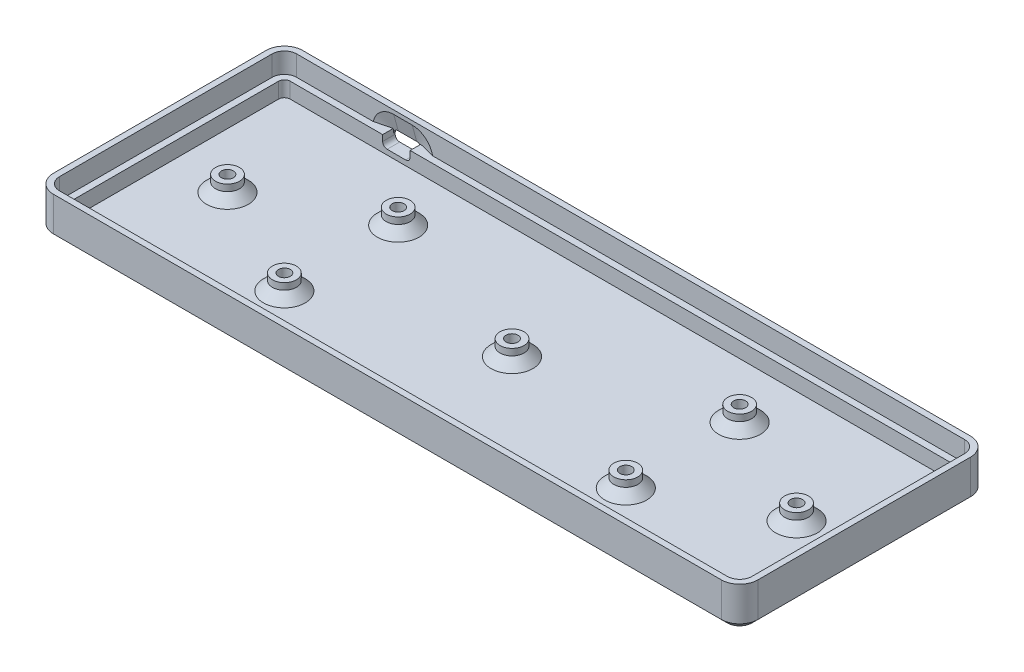
SolidWorks part; units mm, degrees
ref_plane "Alzado" through (0, 0, 0) normal (0, 0, 1) x (1, 0, 0)
ref_plane "Planta" through (0, 0, 0) normal (0, 1, 0) x (1, 0, 0)
ref_plane "Vista lateral" through (0, 0, 0) normal (1, 0, 0) x (0, 0, -1)
sketch "Reference" plane through (0, 0, 0) normal (0, 1, 0) x (1, 0, 0)
  point P0 (0, 0)
  line B0 (-40.625, -35.575) -> (-40.625, -21.575)
  line B1 (-59.675, -35.575) -> (-59.675, -21.575)
  line B2 (-113.775, -35.575) -> (-113.775, 28.575)
  line B3 (-92.725, 16.525) -> (-92.725, 2.525)
  line B4 (-111.775, 37.575) -> (111.775, 37.575)
  circle B5 centre (-104.775, 9.525) radius 2
  line B6 (111.775, -37.575) -> (-111.775, -37.575)
  line B7 (73.675, -21.575) -> (59.675, -21.575)
  circle B8 centre (66.675, -9.525) radius 2
  line B9 (73.675, -2.525) -> (59.675, -2.525)
  line B10 (59.675, 2.525) -> (73.675, 2.525)
  line B11 (73.675, 2.525) -> (73.675, 16.525)
  circle B12 centre (66.675, 9.525) radius 2
  line B13 (73.675, 16.525) -> (59.675, 16.525)
  circle B14 centre (57.15, 19.05) radius 1.35
  line B15 (-40.625, 35.575) -> (-54.625, 35.575)
  line B16 (-97.775, 21.575) -> (-97.775, 35.575)
  circle B17 centre (-104.775, 28.575) radius 2
  line B18 (-111.775, 21.575) -> (-97.775, 21.575)
  line B19 (-97.775, 35.575) -> (-111.775, 35.575)
  line B20 (-111.775, 35.575) -> (-111.775, 21.575)
  line B21 (-113.775, 28.575) -> (-113.775, 35.575)
  arc B22 (-111.775, 37.575) -> (-113.775, 35.575) centre (-111.775, 35.575) ccw
  line B23 (-111.775, 16.525) -> (-111.775, 2.525)
  line B24 (-111.775, 2.525) -> (-97.775, 2.525)
  line B25 (-97.775, -16.525) -> (-97.775, -2.525)
  line B26 (-92.725, -16.525) -> (-78.725, -16.525)
  line B27 (-78.725, -21.575) -> (-92.725, -21.575)
  circle B28 centre (-85.725, -28.575) radius 2
  line B29 (-92.725, -35.575) -> (-78.725, -35.575)
  arc B30 (-113.775, -35.575) -> (-111.775, -37.575) centre (-111.775, -35.575) ccw
  line B31 (-111.775, -35.575) -> (-97.775, -35.575)
  circle B32 centre (-104.775, -28.575) radius 2
  line B33 (-97.775, -21.575) -> (-111.775, -21.575)
  circle B34 centre (-104.775, -9.525) radius 2
  line B35 (-111.775, -16.525) -> (-97.775, -16.525)
  line B36 (-97.775, -35.575) -> (-97.775, -21.575)
  line B37 (-92.725, -21.575) -> (-92.725, -35.575)
  arc B38 (111.775, -37.575) -> (113.775, -35.575) centre (111.775, -35.575) ccw
  line B39 (113.775, 35.575) -> (113.775, -35.575)
  arc B40 (113.775, 35.575) -> (111.775, 37.575) centre (111.775, 35.575) ccw
  line B41 (111.775, 35.575) -> (97.775, 35.575)
  line B42 (97.775, 35.575) -> (97.775, 21.575)
  line B43 (73.675, 21.575) -> (73.675, 35.575)
  circle B44 centre (66.675, 28.575) radius 2
  circle B45 centre (28.575, 28.575) radius 2
  line B46 (-16.525, 35.575) -> (-16.525, 21.575)
  line B47 (-59.675, 35.575) -> (-73.675, 35.575)
  circle B48 centre (-66.675, 28.575) radius 2
  line B49 (-73.675, 35.575) -> (-73.675, 21.575)
  line B50 (-78.725, 2.525) -> (-78.725, 16.525)
  circle B51 centre (-85.725, 9.525) radius 2
  line B52 (-92.725, 2.525) -> (-78.725, 2.525)
  circle B53 centre (-95.25, 0) radius 1.35
  line B54 (-97.775, -2.525) -> (-111.775, -2.525)
  circle B55 centre (-85.725, 28.575) radius 2
  line B56 (-78.725, 21.575) -> (-78.725, 35.575)
  line B57 (-54.625, 35.575) -> (-54.625, 21.575)
  line B58 (-54.625, 21.575) -> (-40.625, 21.575)
  line B59 (-40.625, 16.525) -> (-54.625, 16.525)
  line B60 (-92.725, 35.575) -> (-92.725, 21.575)
  line B61 (-2.525, -16.525) -> (-2.525, -2.525)
  line B62 (16.525, -16.525) -> (16.525, -2.525)
  line B63 (40.625, 2.525) -> (54.625, 2.525)
  line B64 (54.625, 2.525) -> (54.625, 16.525)
  circle B65 centre (47.625, 9.525) radius 2
  line B66 (40.625, 16.525) -> (40.625, 2.525)
  line B67 (35.575, 16.525) -> (21.575, 16.525)
  line B68 (16.525, 16.525) -> (2.525, 16.525)
  line B69 (-16.525, 21.575) -> (-2.525, 21.575)
  circle B70 centre (-28.575, 28.575) radius 2
  line B71 (-21.575, 16.525) -> (-35.575, 16.525)
  circle B72 centre (-57.15, 19.05) radius 1.35
  line B73 (97.775, -35.575) -> (111.775, -35.575)
  line B74 (111.775, -35.575) -> (111.775, -21.575)
  line B75 (111.775, -21.575) -> (97.775, -21.575)
  line B76 (97.775, -2.525) -> (97.775, -16.525)
  line B77 (92.725, 16.525) -> (78.725, 16.525)
  line B78 (78.725, 35.575) -> (78.725, 21.575)
  line B79 (8.438, -18.175) -> (-8.438, -18.175)
  line B80 (7, -21.575) -> (-7, -21.575)
  circle B81 centre (0, -28.575) radius 2
  line B82 (-7, -35.575) -> (7, -35.575)
  line B83 (-111.775, -21.575) -> (-111.775, -35.575)
  line B84 (59.675, 21.575) -> (73.675, 21.575)
  line B85 (59.675, 35.575) -> (59.675, 21.575)
  circle B86 centre (47.625, 28.575) radius 2
  circle B87 centre (-66.675, 9.525) radius 2
  line B88 (-73.675, 16.525) -> (-73.675, 2.525)
  line B89 (-78.725, 16.525) -> (-92.725, 16.525)
  line B90 (-76.2, 39.575) -> (-76.2, 41.575)
  line B91 (-71.2, 39.575) -> (-81.2, 39.575)
  line B92 (-76.2, 37.575) -> (-76.2, 39.575)
  line B93 (-97.775, 2.525) -> (-97.775, 16.525)
  line B94 (-40.625, 21.575) -> (-40.625, 35.575)
  line B95 (-78.725, 35.575) -> (-92.725, 35.575)
  line B96 (-35.575, -35.575) -> (-21.575, -35.575)
  circle B97 centre (-28.575, -28.575) radius 2
  line B98 (-35.575, -21.575) -> (-35.575, -35.575)
  circle B99 centre (-47.625, 28.575) radius 2
  line B100 (-59.675, -21.575) -> (-73.675, -21.575)
  line B101 (-73.675, -16.525) -> (-59.675, -16.525)
  line B102 (-59.675, -2.525) -> (-73.675, -2.525)
  line B103 (-59.675, 2.525) -> (-59.675, 16.525)
  line B104 (-59.675, 21.575) -> (-59.675, 35.575)
  line B105 (-111.775, -2.525) -> (-111.775, -16.525)
  line B106 (-73.675, 21.575) -> (-59.675, 21.575)
  line B107 (-59.675, 16.525) -> (-73.675, 16.525)
  line B108 (-59.675, -16.525) -> (-59.675, -2.525)
  line B109 (-81.2, 39.575) -> (-81.2, 37.575)
  line B110 (-92.725, 21.575) -> (-78.725, 21.575)
  circle B111 centre (-47.625, 9.525) radius 2
  line B112 (-54.625, 16.525) -> (-54.625, 2.525)
  line B113 (-97.775, 16.525) -> (-111.775, 16.525)
  line B114 (-35.575, 16.525) -> (-35.575, 2.525)
  circle B115 centre (-9.525, 9.525) radius 2
  line B116 (2.525, 16.525) -> (2.525, 2.525)
  line B117 (97.775, -21.575) -> (97.775, -35.575)
  circle B118 centre (85.725, -28.575) radius 2
  line B119 (73.675, -35.575) -> (73.675, -21.575)
  line B120 (40.625, -16.525) -> (54.625, -16.525)
  line B121 (21.575, -16.525) -> (35.575, -16.525)
  circle B122 centre (47.625, -9.525) radius 2
  line B123 (54.625, -16.525) -> (54.625, -2.525)
  line B124 (35.575, -16.525) -> (35.575, -2.525)
  line B125 (16.525, -2.525) -> (2.525, -2.525)
  line B126 (-16.525, 2.525) -> (-2.525, 2.525)
  line B127 (-21.575, 2.525) -> (-21.575, 16.525)
  line B128 (-54.625, 2.525) -> (-40.625, 2.525)
  line B129 (-40.625, -2.525) -> (-54.625, -2.525)
  circle B130 centre (-47.625, -9.525) radius 2
  line B131 (-54.625, -16.525) -> (-40.625, -16.525)
  line B132 (-40.625, -21.575) -> (-54.625, -21.575)
  line B133 (-54.625, -21.575) -> (-54.625, -35.575)
  circle B134 centre (-57.15, -19.05) radius 1.35
  circle B135 centre (-85.725, -9.525) radius 2
  line B136 (-78.725, -2.525) -> (-92.725, -2.525)
  line B137 (-73.675, -2.525) -> (-73.675, -16.525)
  line B138 (-21.575, -16.525) -> (-21.575, -2.525)
  circle B139 centre (-9.525, -9.525) radius 2
  line B140 (21.575, -2.525) -> (21.575, -16.525)
  circle B141 centre (28.575, -9.525) radius 2
  line B142 (40.625, -2.525) -> (40.625, -16.525)
  line B143 (54.625, -2.525) -> (40.625, -2.525)
  line B144 (59.675, 16.525) -> (59.675, 2.525)
  line B145 (78.725, 16.525) -> (78.725, 2.525)
  line B146 (92.725, -2.525) -> (78.725, -2.525)
  circle B147 centre (104.775, -9.525) radius 2
  line B148 (97.775, -16.525) -> (111.775, -16.525)
  line B149 (78.725, -21.575) -> (78.725, -35.575)
  circle B150 centre (57.15, -19.05) radius 1.35
  line B151 (92.725, -16.525) -> (92.725, -2.525)
  line B152 (111.775, -2.525) -> (97.775, -2.525)
  line B153 (97.775, 16.525) -> (97.775, 2.525)
  line B154 (-21.575, 21.575) -> (-21.575, 35.575)
  circle B155 centre (28.575, 9.525) radius 2
  circle B156 centre (95.25, 0) radius 1.35
  line B157 (78.725, -16.525) -> (92.725, -16.525)
  circle B158 centre (66.675, -28.575) radius 2
  line B159 (59.675, -21.575) -> (59.675, -35.575)
  line B160 (-7, -21.575) -> (-7, -35.575)
  circle B161 centre (-66.675, -9.525) radius 2
  circle B162 centre (-28.575, 9.525) radius 2
  line B163 (-40.625, 2.525) -> (-40.625, 16.525)
sketch_block_instance "reference_plate-1"
sketch_block "reference_plate"
sketch "Croquis2" plane through (0, 0, 0) normal (0, 1, 0) x (1, 0, 0)
  line L0 (-115.9, 35.575) -> (-115.9, -35.575)
  line L1 (-111.775, -39.7) -> (111.775, -39.7)
  line L2 (115.9, -35.575) -> (115.9, 35.575)
  line L3 (111.775, 39.7) -> (-111.775, 39.7)
  line L4 (111.775, 41.7) -> (-111.775, 41.7)
  line L5 (-117.9, 35.575) -> (-117.9, -35.575)
  line L6 (-111.775, -41.7) -> (111.775, -41.7)
  line L7 (117.9, -35.575) -> (117.9, 35.575)
  line L41 (-115.7, 35.575) -> (-115.7, -35.575) construction
  line L46 (115.7, -35.575) -> (115.7, 35.575)
  line L47 (-111.775, -39.5) -> (111.775, -39.5)
  line L48 (-115.7, 28.575) -> (-115.7, -35.575)
  line L49 (-115.7, 35.575) -> (-115.7, 28.575)
  line L50 (111.775, 39.5) -> (-111.775, 39.5)
  line L51 (115.7, -35.575) -> (115.7, 35.575) construction
  line L52 (-111.775, -39.5) -> (111.775, -39.5) construction
  line L55 (111.775, 39.5) -> (-111.775, 39.5) construction
  arc A0 (-115.9, -35.575) -> (-111.775, -39.7) centre (-111.775, -35.575) ccw
  arc A1 (111.775, -39.7) -> (115.9, -35.575) centre (111.775, -35.575) ccw
  arc A2 (115.9, 35.575) -> (111.775, 39.7) centre (111.775, 35.575) ccw
  arc A3 (-111.775, 39.7) -> (-115.9, 35.575) centre (-111.775, 35.575) ccw
  arc A4 (-111.775, 41.7) -> (-117.9, 35.575) centre (-111.775, 35.575) ccw
  arc A5 (-117.9, -35.575) -> (-111.775, -41.7) centre (-111.775, -35.575) ccw
  arc A6 (111.775, -41.7) -> (117.9, -35.575) centre (111.775, -35.575) ccw
  arc A7 (117.9, 35.575) -> (111.775, 41.7) centre (111.775, 35.575) ccw
  arc A28 (115.7, 35.575) -> (111.775, 39.5) centre (111.775, 35.575) ccw
  arc A29 (111.775, -39.5) -> (115.7, -35.575) centre (111.775, -35.575) ccw
  arc A30 (-115.7, -35.575) -> (-111.775, -39.5) centre (-111.775, -35.575) ccw
  arc A31 (-111.775, 39.5) -> (-115.7, 35.575) centre (-111.775, 35.575) ccw
  arc A32 (115.7, 35.575) -> (111.775, 39.5) centre (111.775, 35.575) ccw construction
  arc A33 (111.775, -39.5) -> (115.7, -35.575) centre (111.775, -35.575) ccw construction
  arc A34 (-115.7, -35.575) -> (-111.775, -39.5) centre (-111.775, -35.575) ccw construction
  arc A35 (-111.775, 39.5) -> (-115.7, 35.575) centre (-111.775, 35.575) ccw construction
  point P0 (-111.775, -39.5)
  dimension "D3" = 1.875
  dimension "D1" = 1.925
  dimension "D2" = 0.2
  dimension "D4" = 2
extrude "Saliente-Extruir1" add sketch "Croquis2" along normal blind 12
sketch "Croquis4" plane through (0, 0, 0) normal (0, -1, 0) x (1, 0, 0)
  line L21 (115.9, 35.575) -> (115.9, -35.575) construction
  line L22 (-111.775, 39.7) -> (111.775, 39.7) construction
  line L23 (-115.9, -35.575) -> (-115.9, 35.575) construction
  line L24 (111.775, -39.7) -> (-111.775, -39.7) construction
  line L25 (113.7, -35.575) -> (113.7, 35.575)
  line L26 (-111.775, -37.5) -> (111.775, -37.5)
  line L27 (111.775, 37.5) -> (-111.775, 37.5)
  line L28 (-113.7, 35.575) -> (-113.7, -35.575)
  line L29 (113.7, -35.575) -> (113.7, 35.575)
  line L30 (-111.775, -37.5) -> (111.775, -37.5)
  line L31 (111.775, 37.5) -> (-111.775, 37.5)
  line L32 (-113.7, 35.575) -> (-113.7, -35.575)
  line L33 (115.9, 35.575) -> (115.9, -35.575)
  line L34 (-111.775, 39.7) -> (111.775, 39.7)
  line L35 (-115.9, -35.575) -> (-115.9, 35.575)
  line L36 (111.775, -39.7) -> (-111.775, -39.7)
  arc A15 (111.775, -39.7) -> (115.9, -35.575) centre (111.775, -35.575) ccw construction
  arc A16 (115.9, 35.575) -> (111.775, 39.7) centre (111.775, 35.575) ccw construction
  arc A17 (-111.775, 39.7) -> (-115.9, 35.575) centre (-111.775, 35.575) ccw construction
  arc A18 (-115.9, -35.575) -> (-111.775, -39.7) centre (-111.775, -35.575) ccw construction
  arc A19 (113.7, 35.575) -> (111.775, 37.5) centre (111.775, 35.575) ccw
  arc A20 (111.775, -37.5) -> (113.7, -35.575) centre (111.775, -35.575) ccw
  arc A21 (-113.7, -35.575) -> (-111.775, -37.5) centre (-111.775, -35.575) ccw
  arc A22 (-111.775, 37.5) -> (-113.7, 35.575) centre (-111.775, 35.575) ccw
  arc A23 (113.7, 35.575) -> (111.775, 37.5) centre (111.775, 35.575) ccw
  arc A24 (111.775, -37.5) -> (113.7, -35.575) centre (111.775, -35.575) ccw
  arc A25 (-113.7, -35.575) -> (-111.775, -37.5) centre (-111.775, -35.575) ccw
  arc A26 (-111.775, 37.5) -> (-113.7, 35.575) centre (-111.775, 35.575) ccw
  arc A27 (111.775, -39.7) -> (115.9, -35.575) centre (111.775, -35.575) ccw
  arc A28 (115.9, 35.575) -> (111.775, 39.7) centre (111.775, 35.575) ccw
  arc A29 (-111.775, 39.7) -> (-115.9, 35.575) centre (-111.775, 35.575) ccw
  arc A30 (-115.9, -35.575) -> (-111.775, -39.7) centre (-111.775, -35.575) ccw
  dimension "D1" = 2.2
extrude "Saliente-Extruir2" add sketch "Croquis4" against normal blind 5.2
sketch "Croquis5" plane through (0, 0, -41.7) normal (0, 0, -1) x (-1, 0, 0)
  line L0 (111.775, 5.2) -> (-111.775, 5.2) construction
  line L1 (111.775, 5.2) -> (-111.775, 5.2) construction
  line L2 (76.2, 0) -> (76.2, 5.2) construction
  line L4 (73.1, 1.7) -> (79.3, 1.7)
  line L5 (71.6, 3.2) -> (71.6, 3.7)
  line L6 (73.1, 5.2) -> (79.3, 5.2)
  line L7 (80.8, 3.2) -> (80.8, 3.7)
  arc A0 (79.3, 1.7) -> (80.8, 3.2) centre (79.3, 3.2) ccw
  arc A1 (73.1, 1.7) -> (71.6, 3.2) centre (73.1, 3.2) cw
  arc A2 (79.3, 5.2) -> (80.8, 3.7) centre (79.3, 3.7) cw
  arc A3 (71.6, 3.7) -> (73.1, 5.2) centre (73.1, 3.7) cw
  point P0 (76.2, 0)
  point P10 (76.2, 1.7)
  point P17 (80.8, 5.2)
  point P20 (71.6, 5.2)
  dimension "D3" = 1.5
  dimension "D1" = 9.2
  dimension "D2" = 3.5
extrude "Cortar-Extruir1" cut sketch "Croquis5" against normal up to next contours L6 A2 L7 A0 L4 A1 L5 A3
sketch "Croquis6" plane through (0, 0, -37.5) normal (0, 0, 1) x (1, 0, 0)
  line L0 (-80.8, 3.2) -> (-80.8, 5.2)
  line L1 (-111.775, 5.2) -> (-79.3, 5.2) construction
  line L2 (-80.8, 5.2) -> (-71.6, 5.2)
  line L3 (-73.1, 5.2) -> (111.775, 5.2) construction
  line L4 (-71.6, 5.2) -> (-71.6, 3.2)
  line L5 (-71.6, 3.2) -> (-80.8, 3.2)
  line L6 (-71.6, 3.7) -> (-71.6, 3.2) construction
  point P5 (-70.5441, 5.2)
extrude "Cortar-Extruir2" cut sketch "Croquis6" against normal up to surface (2.2 mm away) up to face at (-25.4, 7.4667, -39.7)
sketch "Croquis8" plane through (0, 0, 0) normal (0, -1, 0) x (1, 0, 0)
  line L0 (117.9, 35.575) -> (117.9, -35.575) construction
  line L1 (-111.775, 41.7) -> (111.775, 41.7) construction
  line L2 (111.775, -41.7) -> (-111.775, -41.7) construction
  line L3 (-117.9, -35.575) -> (-117.9, 35.575) construction
  line L4 (117.9, 35.575) -> (117.9, -35.575)
  line L5 (-111.775, 41.7) -> (111.775, 41.7)
  line L6 (111.775, -41.7) -> (-111.775, -41.7)
  line L7 (-117.9, -35.575) -> (-117.9, 35.575)
  arc A0 (111.775, -41.7) -> (117.9, -35.575) centre (111.775, -35.575) ccw construction
  arc A1 (117.9, 35.575) -> (111.775, 41.7) centre (111.775, 35.575) ccw construction
  arc A2 (-111.775, 41.7) -> (-117.9, 35.575) centre (-111.775, 35.575) ccw construction
  arc A3 (-117.9, -35.575) -> (-111.775, -41.7) centre (-111.775, -35.575) ccw construction
  arc A4 (111.775, -41.7) -> (117.9, -35.575) centre (111.775, -35.575) ccw
  arc A5 (117.9, 35.575) -> (111.775, 41.7) centre (111.775, 35.575) ccw
  arc A6 (-111.775, 41.7) -> (-117.9, 35.575) centre (-111.775, 35.575) ccw
  arc A7 (-117.9, -35.575) -> (-111.775, -41.7) centre (-111.775, -35.575) ccw
extrude "Saliente-Extruir3" add sketch "Croquis8" along normal blind 1.5
chamfer "Chaflán1" distance 2 angle 45 8 edges at (116.106, -1.5, 39.906) (0, -1.5, 41.7) (-116.106, -1.5, 39.906) (-117.9, -1.5, 0) (-116.106, -1.5, -39.906) (0, -1.5, -41.7) (116.106, -1.5, -39.906) (117.9, -1.5, 0)
sketch "Croquis9" plane through (0, 5.2, 0) normal (0, 1, 0) x (1, 0, 0)
  circle A0 centre (-95.25, 0) radius 4
  circle A1 centre (-57.15, 19.05) radius 4
  circle A2 centre (-57.15, -19.05) radius 4
  circle A3 centre (57.15, -19.05) radius 4
  circle A4 centre (95.25, 0) radius 4
  circle A5 centre (57.15, 19.05) radius 4
  circle A6 centre (0, 0) radius 4
  circle A7 centre (-57.15, 19.05) radius 2
  circle A8 centre (-95.25, 0) radius 2
  circle A9 centre (-57.15, -19.05) radius 2
  circle A10 centre (57.15, -19.05) radius 2
  circle A11 centre (95.25, 0) radius 2
  circle A12 centre (57.15, 19.05) radius 2
  circle A13 centre (0, 0) radius 2
  point P0 (-57.15, 19.05)
  point P1 (-57.15, -19.05)
  point P3 (-95.25, 0)
  point P5 (57.15, 19.05)
  point P7 (95.25, 0)
  point P9 (57.15, -19.05)
  dimension "D1" = 8
  dimension "D2" = 4
extrude "Saliente-Extruir4" add sketch "Croquis9" against normal up to surface (6.7 mm away) up to face at (0, -1.5, 0)
extrude "Cortar-Extruir3" cut sketch "Croquis9<2>" against normal offset from surface (6.2 mm away) 0.5 contours A8 | A7 | A9 | A13 | A12 | A10 | A11 region at (-95.25, 5.2, 0) up to face at (0, -1.5, 0)
sketch "Croquis9<2>" plane through (0, 5.2, 0) normal (0, 1, 0) x (1, 0, 0) same geometry as "Croquis9"
chamfer "Chaflán2" distance 3 angle 45 7 edges at (95.25, 0, -4) (57.15, 0, 15.05) (57.15, 0, -23.05) (0, 0, -4) (-57.15, 0, 15.05) (-57.15, 0, -23.05) (-95.25, 0, -4)
chamfer "Chaflán3" distance 1.5 distance2 5.5 3 edges at (-80.3607, 4.7607, -39.7) (-72.0393, 4.7607, -39.7) (-76.2, 5.2, -39.7) first distance on face at (-80.2053, 4.6053, -40.7) first distance on face at (-72.1947, 4.6053, -40.7) first distance on face at (-76.2, 5.2, -40.7)
